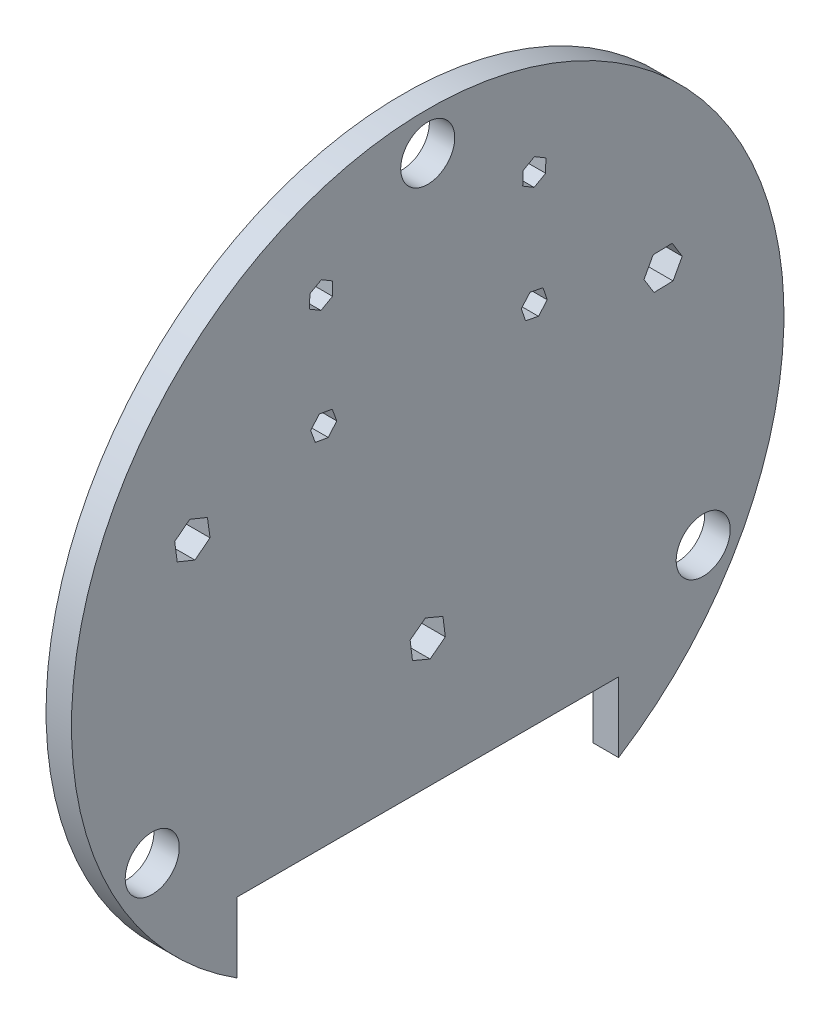
SolidWorks part; units mm, degrees
ref_plane "Ebene vorne" through (0, 0, 0) normal (0, 0, 1) x (1, 0, 0)
ref_plane "Ebene oben" through (0, 0, 0) normal (0, 1, 0) x (1, 0, 0)
ref_plane "Ebene rechts" through (0, 0, 0) normal (1, 0, 0) x (0, 0, -1)
sketch "Sketch1" plane through (0, 0, 0) normal (1, 0, 0) x (0, 0, -1)
  circle A0 centre (0, 0) radius 56
  dimension "D1" = 112
extrude "Boss-Extrude1" add sketch "Sketch1" along normal blind 4
sketch "Sketch2" plane through (0, 0, 0) normal (-1, 0, 0) x (0, 0, 1)
  circle A1 centre (0, 50) radius 4.25
  circle A2 centre (43.3013, -25) radius 4.25
  circle A3 centre (-43.3013, -25) radius 4.25
  point P9 (0, 0)
  point P13 (0, 0)
  dimension "D4" = 3
  dimension "D2" = 50
extrude "Cut-Extrude1" cut sketch "Sketch2" against normal through all
sketch "Sketch3" plane through (0, 0, 0) normal (-1, 0, 0) x (0, 0, 1)
  line L0 (-30, -47.2864) -> (-30, -36.2864)
  line L1 (0, 56) -> (0, -56) construction
  line L2 (30, -47.2864) -> (30, -36.2864)
  line L3 (-30, -36.2864) -> (30, -36.2864)
  circle A0 centre (0, 0) radius 56 construction
  arc A2 (-30, -47.2864) -> (30, -47.2864) centre (0, 0) ccw
  dimension "D1" = 11
  dimension "D2" = 60
extrude "Cut-Extrude2" cut sketch "Sketch3" against normal through all
sketch "Sketch4" plane through (4, 0, 0) normal (1, 0, 0) x (0, 0, -1)
  line L1 (16.7789, 41.137) -> (14.9646, 40.1229)
  line L2 (14.9646, 40.1229) -> (14.9357, 38.0446)
  line L3 (14.9357, 38.0446) -> (16.7211, 36.9805)
  line L4 (16.7211, 36.9805) -> (18.5354, 37.9946)
  line L5 (18.5354, 37.9946) -> (18.5643, 40.0728)
  line L6 (18.5643, 40.0728) -> (16.7789, 41.137)
  line L7 (-16.7226, 41.137) -> (-18.5361, 40.1216)
  line L8 (-18.5361, 40.1216) -> (-18.5635, 38.0433)
  line L9 (-18.5635, 38.0433) -> (-16.7774, 36.9804)
  line L10 (-16.7774, 36.9804) -> (-14.9639, 37.9958)
  line L11 (-14.9639, 37.9958) -> (-14.9365, 40.0741)
  line L12 (-14.9365, 40.0741) -> (-16.7226, 41.137)
  line L13 (16.0882, 23.029) -> (14.7128, 21.4707)
  line L14 (14.7128, 21.4707) -> (15.3746, 19.5005)
  line L15 (15.3746, 19.5005) -> (17.4118, 19.0884)
  line L16 (17.4118, 19.0884) -> (18.7872, 20.6467)
  line L17 (18.7872, 20.6467) -> (18.1254, 22.617)
  line L18 (18.1254, 22.617) -> (16.0882, 23.029)
  line L19 (-17.0612, 23.0152) -> (-18.3947, 21.4209)
  line L20 (-18.3947, 21.4209) -> (-17.6808, 19.4689)
  line L21 (-17.6808, 19.4689) -> (-15.6333, 19.1112)
  line L22 (-15.6333, 19.1112) -> (-14.2998, 20.7055)
  line L23 (-14.2998, 20.7055) -> (-15.0138, 22.6575)
  line L24 (-15.0138, 22.6575) -> (-17.0612, 23.0152)
  line L25 (35.4305, 18.4437) -> (33.9988, 15.8048)
  line L26 (33.9988, 15.8048) -> (35.5684, 13.2455)
  line L27 (35.5684, 13.2455) -> (38.5695, 13.3251)
  line L28 (38.5695, 13.3251) -> (40.0012, 15.964)
  line L29 (40.0012, 15.964) -> (38.4316, 18.5233)
  line L30 (38.4316, 18.5233) -> (35.4305, 18.4437)
  line L31 (-39.7785, 17.0215) -> (-39.3741, 14.0467)
  line L32 (-39.3741, 14.0467) -> (-36.5956, 12.9095)
  line L33 (-36.5956, 12.9095) -> (-34.2215, 14.7472)
  line L34 (-34.2215, 14.7472) -> (-34.6259, 17.7221)
  line L35 (-34.6259, 17.7221) -> (-37.4044, 18.8592)
  line L36 (-37.4044, 18.8592) -> (-39.7785, 17.0215)
  line L37 (-2.7667, -14.9052) -> (-2.3928, -17.8841)
  line L38 (-2.3928, -17.8841) -> (0.374, -19.0496)
  line L39 (0.374, -19.0496) -> (2.7667, -17.2363)
  line L40 (2.7667, -17.2363) -> (2.3928, -14.2575)
  line L41 (2.3928, -14.2575) -> (-0.374, -13.0919)
  line L42 (-0.374, -13.0919) -> (-2.7667, -14.9052)
  circle A0 centre (37, 15.8844) radius 2.6 construction
  circle A1 centre (-16.75, 39.0587) radius 1.8 construction
  circle A2 centre (-37, 15.8844) radius 2.6 construction
  circle A3 centre (0, -16.0708) radius 2.6 construction
  circle A7 centre (16.75, 39.0587) radius 1.8 construction
  circle A8 centre (16.75, 21.0587) radius 1.8 construction
  circle A9 centre (-16.3473, 21.0632) radius 1.8 construction
  dimension "D1" = 5.2
  dimension "D2" = 5.2
  dimension "D3" = 3.6
  dimension "D4" = 3.6
extrude "Cut-Extrude3" cut sketch "Sketch4" against normal through all
